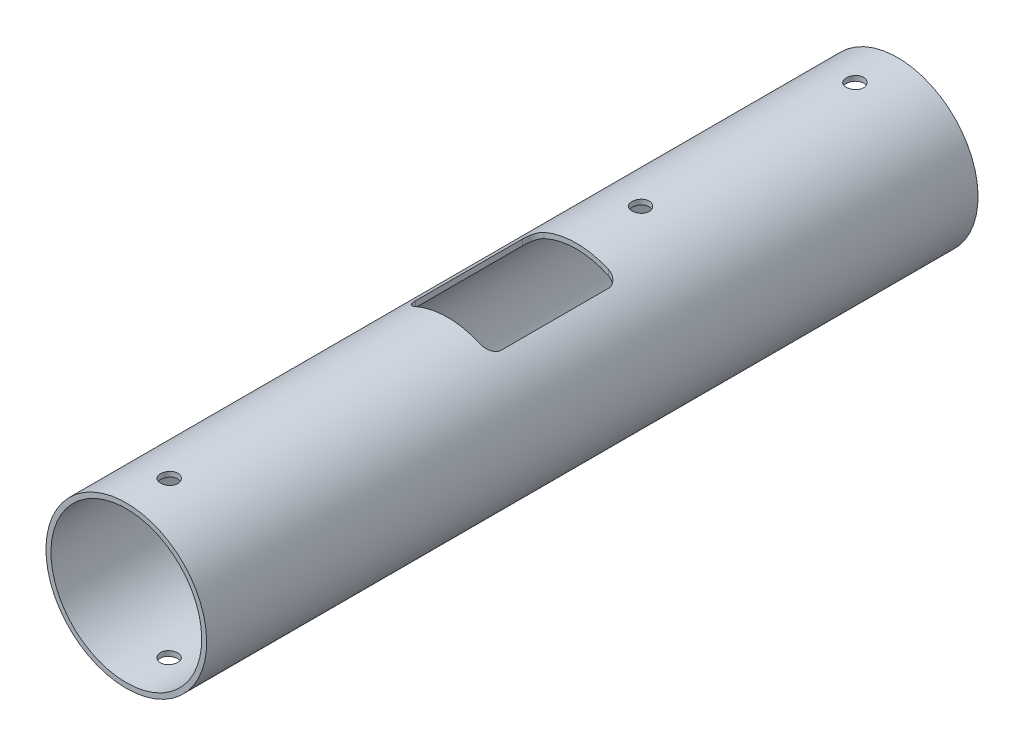
SolidWorks part; units mm, degrees
material "6061-T6 (SS)"
ref_plane "Front Plane" through (0, 0, 0) normal (0, 0, 1) x (1, 0, 0)
ref_plane "Top Plane" through (0, 0, 0) normal (0, 1, 0) x (1, 0, 0)
ref_plane "Right Plane" through (0, 0, 0) normal (1, 0, 0) x (0, 0, -1)
sketch "Sketch1" plane through (0, 0, 0) normal (0, 0, 1) x (1, 0, 0)
  line L0 (23.8125, 0) -> (22.3393, 0) construction
  circle A0 centre (0, 0) radius 23.8125
  circle A1 centre (0, 0) radius 22.3393
  point P4 (22.3393, 0)
  point P5 (23.8125, 0)
  point P6 (0, 23.8125)
  point P7 (0, 22.3393)
  dimension "OD" = 47.625
  dimension "ID" = 44.6786
  dimension "Wall Thickness" = 1.4732
sketch "Sketch2" plane through (0, 0, 0) normal (1, 0, 0) x (0, 0, -1)
  line L0 (-114.3, 0) -> (114.3, 0) construction
  line L2 (-114.3, 23.8125) -> (114.3, 23.8125) construction
  line L3 (-114.3, 23.8125) -> (-114.3, 22.3393) construction
  line L4 (-114.3, 22.3393) -> (114.3, 22.3393) construction
  line L5 (114.3, 23.8125) -> (114.3, 22.3393) construction
  line L7 (-6.35, 0) -> (6.35, 0) construction
  point P4 (0, 0)
  point P19 (0, 0)
  dimension "Length" = 228.6
sketch "Sketch3" plane through (0, 0, 0) normal (1, 0, 0) x (0, 0, -1)
  line L0 (-114.3, 0) -> (114.3, 0) construction
  line L1 (-114.3, 23.8125) -> (114.3, 23.8125)
  line L2 (-114.3, 23.8125) -> (-114.3, 22.3393)
  line L3 (-114.3, 22.3393) -> (114.3, 22.3393)
  line L4 (114.3, 23.8125) -> (114.3, 22.3393)
  line L5 (-114.3, 0) -> (114.3, 0) construction
revolve "Revolve1" add sketch "Sketch3" angle 360 about L5
sketch "Sketch4" plane through (0, 0, 0) normal (0, 1, 0) x (1, 0, 0)
  line L0 (0, 101.6) -> (0, 38.1) construction
  line L1 (23.8125, 114.3) -> (-23.8125, 114.3) construction
  line L2 (44.45, -114.3) -> (-44.45, -114.3) construction
  circle A0 centre (0, 101.6) radius 2.5527
  circle A1 centre (0, 38.1) radius 2.5527
  circle A2 centre (0, -101.6) radius 2.5527
  dimension "D1" = 5.1054
  dimension "D2" = 12.7
  dimension "D3" = 76.2
  dimension "D4" = 12.7
extrude "Cut-Extrude1" cut sketch "Sketch4" against normal through all both and the other way through all
sketch "Sketch5" plane through (0, 0, 0) normal (0, 1, 0) x (1, 0, 0)
  line L1 (9.525, -19.05) -> (-9.525, -19.05)
  line L2 (12.7, -15.875) -> (12.7, 15.875)
  line L3 (9.525, 19.05) -> (-9.525, 19.05)
  line L4 (-12.7, -15.875) -> (-12.7, 15.875)
  line L5 (12.7, -19.05) -> (-12.7, 19.05) construction
  line L6 (12.7, 19.05) -> (-12.7, -19.05) construction
  arc A0 (-9.525, -19.05) -> (-12.7, -15.875) centre (-9.525, -15.875) cw
  arc A1 (9.525, -19.05) -> (12.7, -15.875) centre (9.525, -15.875) ccw
  arc A2 (12.7, 15.875) -> (9.525, 19.05) centre (9.525, 15.875) ccw
  arc A3 (-9.525, 19.05) -> (-12.7, 15.875) centre (-9.525, 15.875) ccw
  point P0 (0, 0)
  dimension "D1" = 3.175
  dimension "D2" = 25.4
  dimension "D3" = 38.1
extrude "Cut-Extrude2" cut sketch "Sketch5" along normal through all
equation "\"ID@Sketch1\"=\"OD@Sketch1\"-(2*\"Wall Thickness@Sketch1\")"
